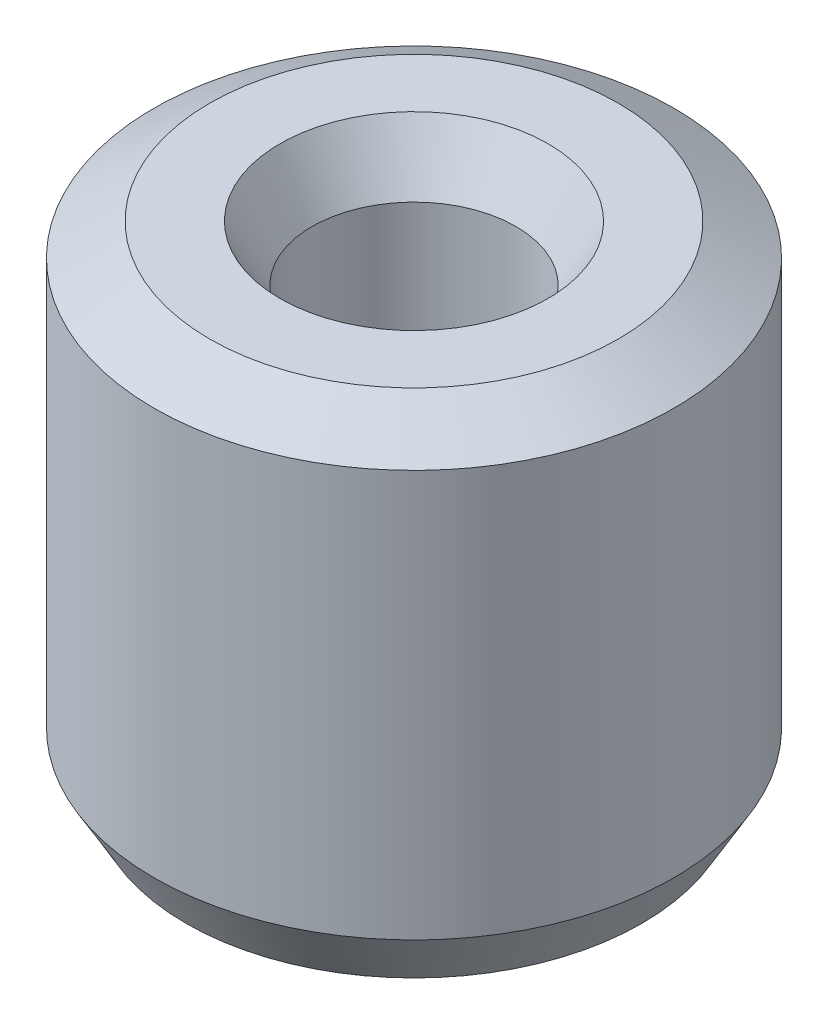
SolidWorks part; units mm, degrees
ref_plane "Front Plane" through (0, 0, 0) normal (0, 0, 1) x (1, 0, 0)
ref_plane "Top Plane" through (0, 0, 0) normal (0, 1, 0) x (1, 0, 0)
ref_plane "Right Plane" through (0, 0, 0) normal (1, 0, 0) x (0, 0, -1)
sketch "Sketch1" plane through (0, 0, 0) normal (0, 1, 0) x (1, 0, 0)
  circle A0 centre (0, 0) radius 12.5
  dimension "SLEEVE_OD" = 25
extrude "Boss-Extrude1" add sketch "Sketch1" along normal blind 23.7764
sketch "Sketch2" plane through (0, 0, 0) normal (0, 1, 0) x (1, 0, 0)
  circle A0 centre (0, 0) radius 4.9037
  dimension "BORE_D" = 9.8075
extrude "Cut-Extrude1" cut sketch "Sketch2" along normal through all
chamfer "Chamfer1" distance 1.5443 angle 60 4 edges at (0, 23.7764, 4.9037) (0, 0, 4.9037) (0, 0, 12.5) (0, 23.7764, 12.5) first distance on face at (0, 23.7764, 4.9037) first distance on face at (0, 0, 4.9037) first distance on face at (0, 23.7764, 12.5)
